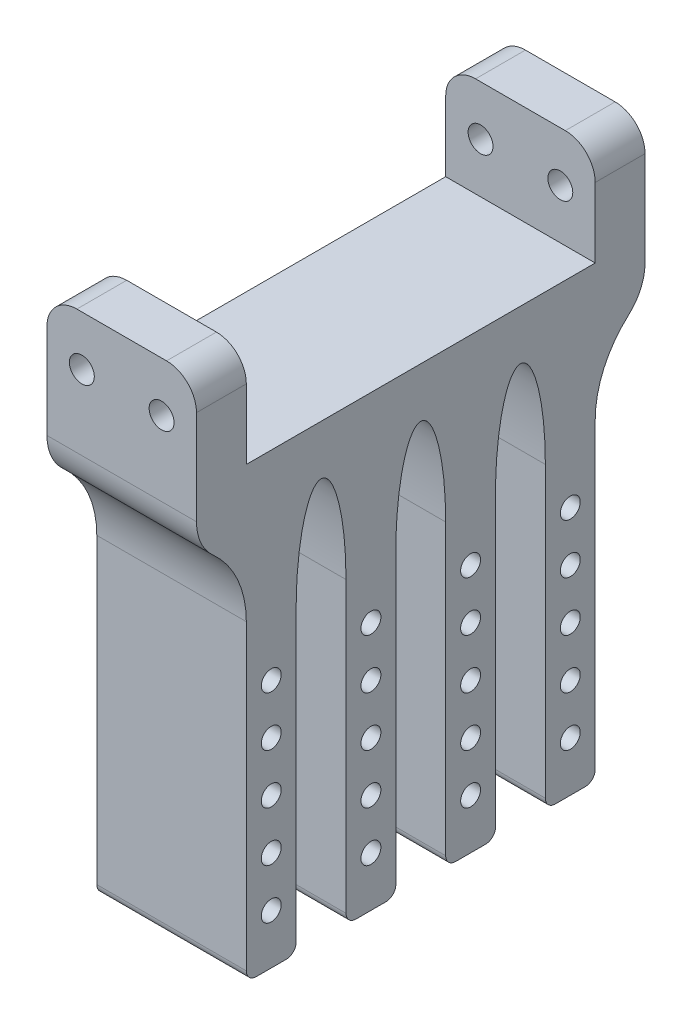
SolidWorks part; units mm, degrees
ref_plane "前视基准面" through (0, 0, 0) normal (0, 0, 1) x (1, 0, 0)
ref_plane "上视基准面" through (0, 0, 0) normal (0, 1, 0) x (1, 0, 0)
ref_plane "右视基准面" through (0, 0, 0) normal (1, 0, 0) x (0, 0, -1)
other "Configuration Table"
sketch "草图3" plane through (0, 0, 0) normal (1, 0, 0) x (0, 0, -1)
  line L1 (0, 0) -> (45, 0)
  line L2 (0, 0) -> (0, 5)
  line L3 (0, 5) -> (45, 5)
  line L4 (45, 0) -> (45, 5)
  dimension "D1" = 45
  dimension "D2" = 5
extrude "凸台-拉伸2" add sketch "草图3" along normal blind 15
sketch "草图4" plane through (0, 5, 0) normal (0, 1, 0) x (1, 0, 0)
  line L0 (15, 45) -> (15, 0) construction
  line L1 (0, 45) -> (15, 45)
  line L2 (0, 45) -> (0, 40)
  line L3 (0, 40) -> (15, 40)
  line L4 (15, 45) -> (15, 40)
  line L6 (0, 0) -> (15, 0)
  line L7 (0, 0) -> (0, 5)
  line L8 (0, 5) -> (15, 5)
  line L9 (15, 0) -> (15, 5)
  dimension "D1" = 5
  dimension "D2" = 5
extrude "凸台-拉伸3" add sketch "草图4" along normal blind 10
sketch "草图6" plane through (0, 0, 0) normal (0, 0, 1) x (1, 0, 0)
  line L0 (0, 10) -> (15, 10) construction
  line L1 (0, 15) -> (0, 0) construction
  line L2 (15, 15) -> (15, 0) construction
  line L3 (0, 15) -> (15, 15) construction
  circle A0 centre (3.5, 10) radius 1.25
  circle A1 centre (11.5, 10) radius 1.25
  dimension "D2" = 2.5
  dimension "D3" = 2.5
  dimension "D1" = 5
  dimension "D4" = 8
  dimension "D5" = 3.5
extrude "切除-拉伸3" cut sketch "草图6" against normal blind 50
fillet "圆角3" radius 3 4 edges at (15, 15, -2.5) (0, 15, -2.5) (15, 15, -42.5) (0, 15, -42.5)
sketch "草图7" plane through (0, 0, 0) normal (0, -1, 0) x (-1, 0, 0)
  line L10 (-15, 22.5) -> (0, 22.5) construction
  line L23 (-15, 0) -> (-15, 45) construction
  line L24 (0, 0) -> (0, 45) construction
  line L26 (-15, 30) -> (0, 30)
  line L27 (-15, 30) -> (-15, 25)
  line L28 (-15, 25) -> (0, 25)
  line L29 (0, 30) -> (0, 25)
  line L30 (-15, 20) -> (0, 20)
  line L31 (-15, 20) -> (-15, 15)
  line L32 (-15, 15) -> (0, 15)
  line L33 (0, 20) -> (0, 15)
  line L34 (-15, 40) -> (0, 40)
  line L35 (-15, 40) -> (-15, 35)
  line L36 (-15, 35) -> (0, 35)
  line L37 (0, 40) -> (0, 35)
  line L38 (-15, 10) -> (0, 10)
  line L39 (-15, 10) -> (-15, 5)
  line L40 (-15, 5) -> (0, 5)
  line L41 (0, 10) -> (0, 5)
  dimension "D1" = 5
  dimension "D2" = 5
  dimension "D3" = 5
  dimension "D4" = 5
  dimension "D5" = 5
  dimension "D6" = 5
  dimension "D7" = 5
  dimension "D8" = 2.5
extrude "凸台-拉伸4" add sketch "草图7" along normal blind 40
fillet "圆角4" radius 10 2 edges at (7.5, 0, -5) (7.5, 0, -40)
fillet "圆角5" radius 5 2 edges at (7.5, 0, 0) (7.5, 0, -45)
fillet "圆角6" radius 1 8 edges at (7.5, -40, -40) (7.5, -40, -35) (7.5, -40, -30) (7.5, -40, -25) (7.5, -40, -20) (7.5, -40, -15) (7.5, -40, -10) (7.5, -40, -5)
fillet "圆角7" radius 2.5 6 edges at (7.5, 0, -10) (7.5, 0, -15) (7.5, 0, -20) (7.5, 0, -25) (7.5, 0, -30) (7.5, 0, -35) second distance 10 first distance on face at (7.5, 0, -12.5) first distance on face at (7.5, 0, -22.5) first distance on face at (7.5, 0, -32.5)
sketch "草图8" plane through (0, 0, 0) normal (-1, 0, 0) x (0, 0, 1)
  line L0 (-27.5, -40) -> (-27.5, -5.1594) construction
  line L1 (-26, -40) -> (-29, -40) construction
  circle A0 centre (-27.5, -15) radius 1
  circle A1 centre (-27.5, -20) radius 1
  circle A2 centre (-27.5, -25) radius 1
  circle A3 centre (-27.5, -30) radius 1
  circle A4 centre (-27.5, -35) radius 1
  point P16 (-27, -34.7155)
  point P17 (0, 0)
  dimension "D1" = 2
  dimension "D2" = 2
  dimension "D3" = 2
  dimension "D4" = 2
  dimension "D8" = 2
  dimension "D5" = 5
  dimension "D6" = 5
  dimension "D7" = 5
  dimension "D9" = 5
  dimension "D10" = 5
extrude "切除-拉伸4" cut sketch "草图8" against normal blind 40
ref_plane "基准面1" through (0, 0, -32.5) normal (0, 0, -1) x (-1, 0, 0)
ref_plane "基准面2" through (0, 0, -22.5) normal (0, 0, -1) x (-1, 0, 0)
mirror "镜向1" about plane through (0, 0, -32.5) normal (0, 0, -1) of "切除-拉伸4" second plane through (0, 0, -22.5) second plane normal (0, 0, -1)
mirror "镜向2" about plane through (0, 0, -22.5) normal (0, 0, -1) of "镜向1"
